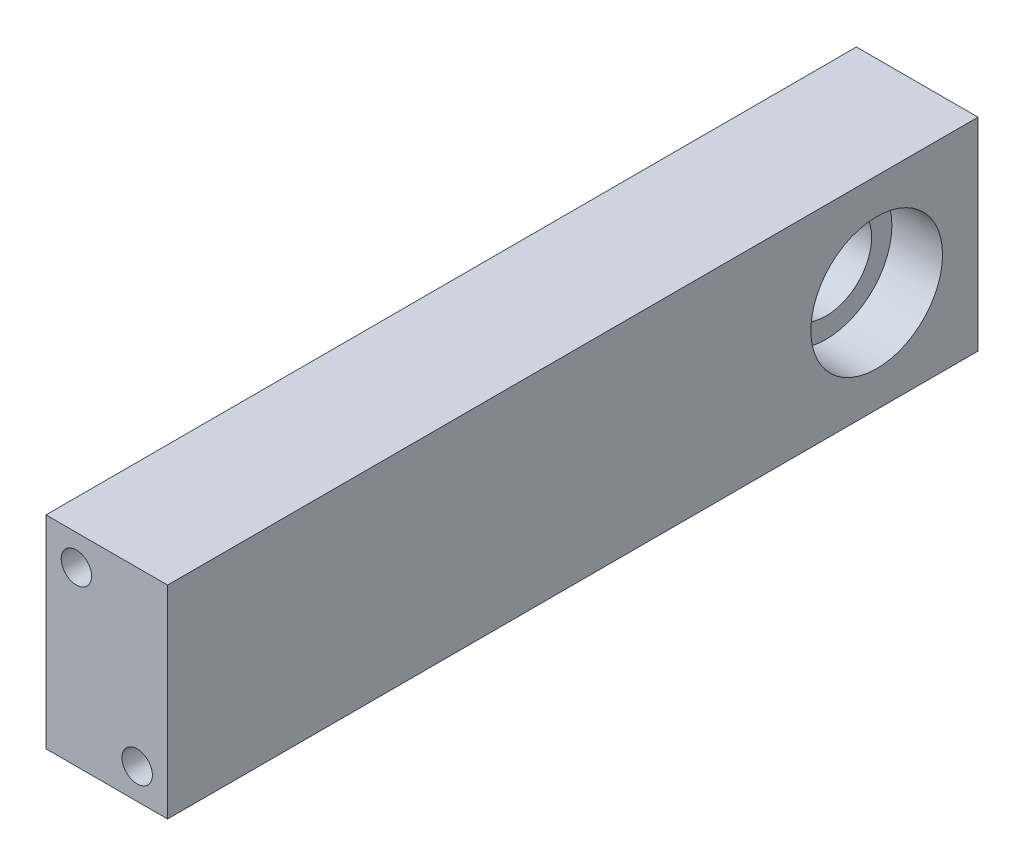
SolidWorks part; units mm, degrees
ref_plane "Płaszczyzna przednia" through (0, 0, 0) normal (0, 0, 1) x (1, 0, 0)
ref_plane "Płaszczyzna górna" through (0, 0, 0) normal (0, 1, 0) x (1, 0, 0)
ref_plane "Płaszczyzna prawa" through (0, 0, 0) normal (1, 0, 0) x (0, 0, -1)
sketch "Szkic1" plane through (0, 0, 0) normal (0, 0, 1) x (1, 0, 0)
  line L1 (-6, -10) -> (6, -10)
  line L2 (-6, -10) -> (-6, 10)
  line L3 (-6, 10) -> (6, 10)
  line L4 (6, -10) -> (6, 10)
  line L5 (-6, -10) -> (6, 10) construction
  line L6 (-6, 10) -> (6, -10) construction
  point P0 (0, 0)
  dimension "D1" = 20
  dimension "D2" = 12
extrude "Dodanie-wyciągnięcie1" add sketch "Szkic1" along normal blind 80
sketch "Szkic2" plane through (0, 0, 80) normal (0, 0, 1) x (1, 0, 0)
  line L0 (6, -10) -> (6, 10) construction
  line L1 (-6, -10) -> (6, -10) construction
  line L2 (-6, 10) -> (-6, -10) construction
  line L3 (6, 10) -> (-6, 10) construction
  circle A0 centre (-3, 7) radius 1.5
  circle A1 centre (3, -7) radius 1.5
  dimension "D1" = 3
  dimension "D2" = 3
  dimension "D3" = 3
  dimension "D4" = 3
  dimension "D5" = 3
  dimension "D6" = 3
extrude "Wytnij-wyciągnięcie1" cut sketch "Szkic2" against normal blind 10
sketch "Szkic4" plane through (6, 0, 0) normal (1, 0, 0) x (0, 0, -1)
  line L0 (-80, 10) -> (0, 10) construction
  line L1 (-80, -10) -> (-80, 10) construction
  circle A0 centre (-10, 0) radius 6.5
  dimension "D1" = 13
  dimension "D2" = 10
  dimension "D3" = 70
extrude "Wytnij-wyciągnięcie2" cut sketch "Szkic4" against normal blind 5
sketch "Szkic5" plane through (-6, 0, 0) normal (-1, 0, 0) x (0, 0, 1)
  line L0 (80, -10) -> (0, -10) construction
  line L1 (80, 10) -> (80, -10) construction
  circle A0 centre (10, 0) radius 4.5
  dimension "D1" = 9
  dimension "D2" = 10
  dimension "D3" = 70
extrude "Wytnij-wyciągnięcie3" cut sketch "Szkic5" against normal through all
